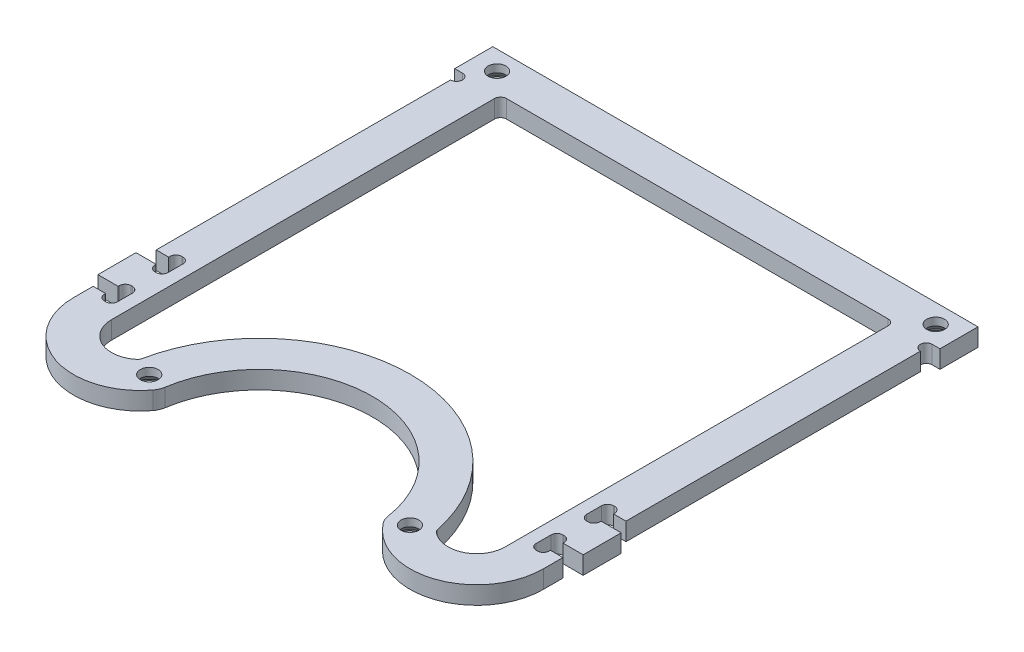
SolidWorks part; units mm, degrees
ref_plane "Front Plane" through (0, 0, 0) normal (0, 0, 1) x (1, 0, 0)
ref_plane "Top Plane" through (0, 0, 0) normal (0, 1, 0) x (1, 0, 0)
ref_plane "Right Plane" through (0, 0, 0) normal (1, 0, 0) x (0, 0, -1)
sketch "Sketch1" plane through (0, 0, 0) normal (0, 1, 0) x (1, 0, 0)
  line L0 (-36.88, 36.725) -> (36.88, 36.725) construction
  line L1 (36.88, 36.725) -> (21.92, -36.725) construction
  line L2 (21.92, -36.725) -> (-21.92, -36.725) construction
  line L3 (-21.92, -36.725) -> (-36.88, 36.725) construction
  line L4 (0, -40.095) -> (0, -36.725) construction
  line L5 (0, 36.725) -> (0, -36.725) construction
  line L6 (-39.5, -14.675) -> (-39.5, 33.525)
  line L7 (-33.1, -14.675) -> (-33.1, 33.525)
  line L8 (-39.5, 9.425) -> (-33.1, 9.425) construction
  line L9 (0, 33.525) -> (0, 39.925) construction
  line L10 (-39.5, -23.275) -> (-33.1, -23.275) construction
  line L13 (40.8, 33.525) -> (-40.8, 33.525)
  line L14 (40.8, 33.525) -> (40.8, 39.925)
  line L15 (40.8, 39.925) -> (-40.8, 39.925)
  line L16 (-40.8, 33.525) -> (-40.8, 39.925)
  line L17 (40.8, 33.525) -> (-40.8, 39.925) construction
  line L18 (40.8, 39.925) -> (-40.8, 33.525) construction
  line L19 (39.5, 33.525) -> (-39.5, 33.525)
  line L20 (39.5, 33.525) -> (39.5, 39.925)
  line L21 (39.5, 39.925) -> (-39.5, 39.925)
  line L22 (-39.5, 33.525) -> (-39.5, 39.925)
  line L23 (39.5, 33.525) -> (-39.5, 39.925) construction
  line L24 (39.5, 39.925) -> (-39.5, 33.525) construction
  line L27 (-35.2, -25.275) -> (-37.4, -25.275)
  line L28 (-39.5, -20.075) -> (-40.8, -20.075)
  line L29 (-35.2, -16.775) -> (-35.2, -14.675) construction
  line L30 (-33.1, -31.875) -> (-39.5, -31.875)
  line L31 (-33.1, -31.875) -> (-33.1, -14.675)
  line L32 (-33.1, -14.675) -> (-39.5, -14.675)
  line L33 (-39.5, -31.875) -> (-39.5, -14.675)
  line L34 (-33.1, -31.875) -> (-39.5, -14.675) construction
  line L35 (-33.1, -14.675) -> (-39.5, -31.875) construction
  line L36 (-39.5, -20.075) -> (-37.4, -20.075)
  line L37 (-39.5, -20.075) -> (-39.5, -17.975)
  line L38 (-39.5, -17.975) -> (-37.4, -17.975)
  line L39 (-37.4, -20.075) -> (-37.4, -17.975)
  line L40 (-37.4, -19.025) -> (-39.5, -19.025) construction
  line L41 (-37.4, -19.025) -> (-33.1, -19.025) construction
  line L42 (-36.3, -31.875) -> (-36.3, -14.675) construction
  line L43 (-35.2, -21.275) -> (-37.4, -21.275)
  line L44 (-35.2, -21.275) -> (-35.2, -16.775)
  line L45 (-35.2, -16.775) -> (-37.4, -16.775)
  line L46 (-37.4, -21.275) -> (-37.4, -16.775)
  line L47 (-35.2, -21.275) -> (-37.4, -16.775) construction
  line L48 (-35.2, -16.775) -> (-37.4, -21.275) construction
  line L53 (-35.2, -25.275) -> (-35.2, -29.775)
  line L58 (-35.2, -29.775) -> (-37.4, -29.775)
  line L67 (39.5, -17.975) -> (37.4, -17.975)
  line L68 (-37.4, -25.275) -> (-37.4, -29.775)
  line L69 (-39.5, -28.575) -> (-37.4, -28.575)
  line L70 (-39.5, -20.075) -> (-39.5, -26.475)
  line L71 (-39.5, -26.475) -> (-40.8, -26.475)
  line L72 (-40.8, -20.075) -> (-40.8, -26.475)
  line L73 (-39.5, -20.075) -> (-40.8, -26.475) construction
  line L74 (-39.5, -26.475) -> (-40.8, -20.075) construction
  line L75 (-39.5, -26.475) -> (-37.4, -26.475)
  line L76 (39.5, -20.075) -> (37.4, -20.075)
  line L77 (39.5, -28.575) -> (37.4, -28.575)
  line L78 (39.5, -26.475) -> (37.4, -26.475)
  line L79 (37.4, -25.275) -> (37.4, -29.775)
  line L80 (35.2, -29.775) -> (37.4, -29.775)
  line L81 (35.2, -25.275) -> (35.2, -29.775)
  line L82 (35.2, -25.275) -> (37.4, -25.275)
  line L83 (35.2, -21.275) -> (37.4, -21.275)
  line L84 (35.2, -21.275) -> (35.2, -16.775)
  line L85 (35.2, -16.775) -> (37.4, -16.775)
  line L86 (37.4, -21.275) -> (37.4, -16.775)
  line L87 (39.5, -17.975) -> (37.4, -17.975)
  line L88 (39.5, -20.075) -> (40.8, -20.075)
  line L89 (40.8, -20.075) -> (40.8, -26.475)
  line L90 (39.5, -26.475) -> (40.8, -26.475)
  line L91 (39.5, -31.875) -> (39.5, -14.675)
  line L92 (33.1, -31.875) -> (33.1, -14.675)
  line L93 (33.1, -14.675) -> (33.1, 33.525)
  line L94 (39.5, -14.675) -> (39.5, 33.525)
  circle A0 centre (21.92, -36.725) radius 1.5
  circle A1 centre (-21.92, -36.725) radius 1.5
  circle A2 centre (-36.88, 36.725) radius 1.5
  circle A3 centre (36.88, 36.725) radius 1.5
  circle A4 centre (-36.88, 36.725) radius 3.2
  circle A5 centre (-21.92, -36.725) radius 3.2
  circle A6 centre (21.92, -36.725) radius 3.2
  circle A7 centre (36.88, 36.725) radius 3.2
  circle A8 centre (0, -40.095) radius 16
  circle A9 centre (0, -40.095) radius 25.3775
  circle A10 centre (0, -40.095) radius 18.9775
  arc A11 (-39.5, -31.875) -> (-19.3737, -38.6631) centre (-28.2921, -31.875) ccw
  arc A12 (-33.1, -31.875) -> (-24.4663, -34.7869) centre (-28.2921, -31.875) ccw
  arc A13 (33.1, -31.875) -> (24.4663, -34.7869) centre (28.2921, -31.875) cw
  arc A14 (39.5, -31.875) -> (19.3737, -38.6631) centre (28.2921, -31.875) cw
  circle A15 centre (-39.5, 32.525) radius 1
  circle A16 centre (39.5, 32.525) radius 1
  point P10 (0, 0)
  point P26 (0, -23.275)
  point P29 (-40.15, -23.275)
  point P37 (-36.3, -23.275)
  point P53 (-36.3, -19.025)
  dimension "D4" = 3
  dimension "D5" = 6.4
  dimension "D6" = 32
  dimension "D11" = 2
  dimension "D1" = 74.958
  dimension "D2" = 43.84
  dimension "D3" = 73.76
  dimension "D7" = 3.37
  dimension "D8" = 81.6
  dimension "D9" = 60
  dimension "D10" = 79
  dimension "D12" = 2.1
  dimension "D13" = 2.2
  dimension "D14" = 4.5
extrude "Shape" add sketch "Sketch1" along normal blind 3 contours A13 A9 A12 A5 A10 A6 | A5 A1 | A9 A11 A5 | A12 A9 A5 | A12 L30 A11 A9 | L33 L75 L68 L27 L53 L58 L69 L30 L31 L32 L38 L46 L45 L44 L43 L36 | L28 L72 L71 L33 | A15 L6 L32 L7 L13 L19 | A4 L22 L15 L16 L13 | A4 L21 L22 | A4 L22 A2 | L22 A4 | A4 L22 L19 | A7 L21 A4 L13 L19 | A7 L20 A3 | A7 L20 L13 L14 L15 | L20 A7 | A7 L13 L20 | L94 A16 L13 L19 L93 L92 A13 A9 A14 L91 L77 L79 L80 L81 L82 L78 L76 L86 L83 L84 L85 L67 | A7 L20 L15 | L91 L90 L89 L88 | A9 A13 A6 | A6 A0 | A14 A9 A6 region at (-36.2858, 0, -9.3068) region at (-36.0672, 0, 23.275) region at (-38.8761, 0, -33.9129) region at (-40.2377, 0, -36.725) region at (0, 0, -36.725) region at (-32.2904, 0, 37.7071) region at (-40.15, 0, 23.275) region at (-38.3167, 0, -33.9628) region at (-39.7339, 0, -36.725) region at (35.4284, 0, 5.7836) region at (-24.8633, 0, 35.4035) region at (0, 0, 15.2643) region at (-38.8761, 0, -39.5371) region at (38.8761, 0, -33.9129) region at (33.7665, 0, -36.725) region at (-23.7462, 0, 40.4359) region at (24.8633, 0, 35.4035) region at (-24.7821, 0, 35.5096) region at (40.2377, 0, -36.725) region at (38.8761, 0, -39.5371) region at (39.7339, 0, -36.725) region at (23.7462, 0, 40.4359) region at (25.0204, 0, 36.4881) region at (40.15, 0, 23.275)
fillet "Mill fillets" radius 1 20 edges at (37.4, 1.5, 21.275) (35.2, 1.5, 21.275) (35.2, 1.5, 16.775) (37.4, 1.5, 16.775) (37.4, 1.5, 25.275) (35.2, 1.5, 25.275) (37.4, 1.5, 29.775) (35.2, 1.5, 29.775) (-37.4, 1.5, 21.275) (-35.2, 1.5, 21.275) (-35.2, 1.5, 16.775) (-37.4, 1.5, 16.775) (-37.4, 1.5, 25.275) (-35.2, 1.5, 25.275) (-35.2, 1.5, 29.775) (-37.4, 1.5, 29.775) (-24.921, 1.5, 35.303) (24.921, 1.5, 35.303) (33.1, 1.5, -33.525) (-33.1, 1.5, -33.525)
hole_wizard "M3 countersunks" positions "Sketch2" profile "Sketch3" countersink size "M3" standard "ANSI Metric" end condition through all
sketch "Sketch2" plane through (0, 0, 0) normal (0, -1, 0) x (-1, 0, 0)
  point P0 (21.92, -36.725)
  point P3 (-21.92, -36.725)
  point P6 (-36.88, 36.725)
  point P9 (36.88, 36.725)
sketch "Sketch3" plane through (-21.92, 0, 36.725) normal (1, 0, 0) x (0, 0, -1)
  line L0 (0, 0) -> (0, 3)
  line L1 (0, 3) -> (1.5, 3)
  line L2 (1.5, 3) -> (1.5, 1.7)
  line L3 (1.5, 1.7) -> (3, 0.2)
  line L4 (3, 0.2) -> (3, 0)
  line L6 (3, 0) -> (0, 0)
  line L7 (-1.5, 1.7) -> (-3, 0.2) construction
  line L11 (0, -6.35) -> (0, 107.95) construction
  dimension "Thru Hole Dia." = 3
  dimension "Thru Hole Depth" = 3
  dimension "C'Sink Dia." = 6
  dimension "C'Sink Angle" = 90
  dimension "Head Clearance" = 0.2
